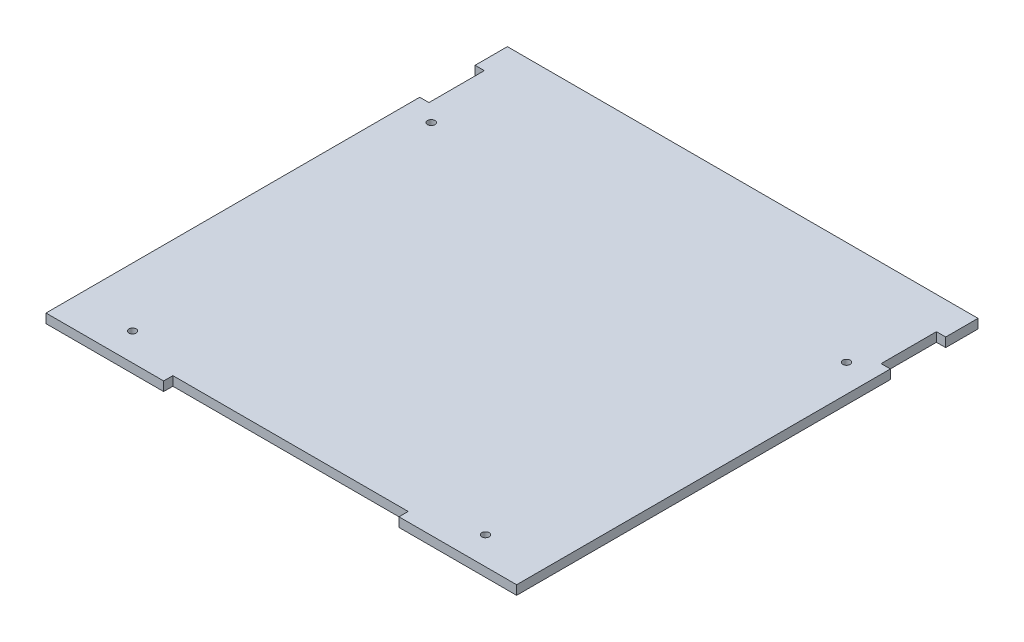
SolidWorks part; units mm, degrees
ref_plane "Front Plane" through (0, 0, 0) normal (0, 0, 1) x (1, 0, 0)
ref_plane "Top Plane" through (0, 0, 0) normal (0, 1, 0) x (1, 0, 0)
ref_plane "Right Plane" through (0, 0, 0) normal (1, 0, 0) x (0, 0, -1)
sketch "Sketch2" plane through (0, 0, 0) normal (0, 1, 0) x (1, 0, 0)
  line L1 (0, 0) -> (255, 0)
  line L2 (0, 0) -> (0, 65)
  line L3 (0, 65) -> (255, 65)
  line L4 (255, 0) -> (255, 65)
extrude "Boss-Extrude1" add sketch "Sketch2" along normal blind 5
sketch "Sketch3" plane through (0, 5, 0) normal (0, 1, 0) x (1, 0, 0)
  line L0 (255, 65) -> (261, 65)
  line L1 (261, 65) -> (261, 0)
  line L2 (261, 0) -> (255, 0)
  line L3 (255, 0) -> (255, 65)
  line L4 (255, 0) -> (255, 17.5)
  line L5 (255, 0) -> (255, 17.5)
  line L6 (255, 17.5) -> (250, 17.5)
  line L7 (250, 17.5) -> (250, 47.5)
  line L8 (250, 47.5) -> (255, 47.5)
  line L9 (255, 47.5) -> (255, 17.5)
  line L10 (127.5, 65) -> (127.5, 23.845)
  line L11 (255, 65) -> (0, 65) construction
  line L12 (0, 47.5) -> (0, 17.5)
  line L13 (5, 47.5) -> (0, 47.5)
  line L14 (5, 17.5) -> (5, 47.5)
  line L15 (0, 17.5) -> (5, 17.5)
  line L16 (0, 0) -> (0, 17.5)
  line L17 (0, 0) -> (0, 17.5)
  line L18 (0, 0) -> (0, 65)
  line L19 (-6, 0) -> (0, 0)
  line L20 (-6, 65) -> (-6, 0)
  line L21 (0, 65) -> (-6, 65)
  line M8 (255, 0) -> (255, 65)
extrude "Boss-Extrude2" add sketch "Sketch3" against normal up to surface (5 mm away) contours L2 L1 L0 L3 M8 | L18 L21 L20 L19 region at (258, 5, -32.5) up to face at (127.5, 0, -32.5)
extrude "Cut-Extrude1" cut sketch "Sketch3<3>" against normal blind 10 contours L15 L14 L13 L12 | L6 L7 L8 L9
sketch "Sketch3<3>" plane through (0, 5, 0) normal (0, 1, 0) x (1, 0, 0) same geometry as "Sketch3"
sketch "Sketch4" plane through (0, 0, 0) normal (0, -1, 0) x (1, 0, 0)
  line L0 (255, -47.5) -> (255, -65)
  line L1 (261, -65) -> (-6, -65) construction
  line L2 (255, -65) -> (261, -65)
  line L3 (261, -65) -> (261, 0)
  line L4 (261, 0) -> (255, 0)
  line L5 (-6, 0) -> (261, 0) construction
  line L6 (255, 0) -> (255, -47.5)
  line L8 (-6, -65) -> (0, -65)
  line L9 (-6, -65) -> (-6, 0)
  line L10 (-6, 0) -> (0, 0)
  line L11 (0, -65) -> (0, 0)
extrude "Cut-Extrude2" cut sketch "Sketch4" against normal blind 10
sketch "Sketch6" plane through (0, 0, 0) normal (0, 0, 1) x (1, 0, 0)
  line L1 (255, 0) -> (0, 0)
  line L2 (255, 0) -> (255, 5)
  line L3 (255, 5) -> (0, 5)
  line L4 (0, 0) -> (0, 5)
extrude "Boss-Extrude3" add sketch "Sketch6" along normal blind 185
sketch "Sketch8" plane through (0, 5, 0) normal (0, 1, 0) x (1, 0, 0)
  line L0 (255, -185) -> (0, -185) construction
  line L1 (127.5, -185) -> (191.25, -185)
  line L3 (127.5, -180) -> (191.25, -180)
  line L7 (127.5, -185) -> (63.75, -185)
  line L9 (127.5, -180) -> (63.75, -180)
  line L11 (191.25, -185) -> (191.25, -180)
  line L12 (63.75, -180) -> (63.75, -185)
extrude "Cut-Extrude3" cut sketch "Sketch8" against normal blind 185
sketch "Sketch9" plane through (0, 5, 0) normal (0, 1, 0) x (1, 0, 0)
  line L0 (223.125, -185) -> (223.125, -170)
  line L1 (255, -185) -> (191.25, -185) construction
  line L2 (127.5, -180) -> (127.5, -159.0905)
  line L3 (191.25, -180) -> (63.75, -180) construction
  circle A0 centre (223.125, -170) radius 1.5
  circle A1 centre (31.875, -170) radius 1.5
extrude "Cut-Extrude4" cut sketch "Sketch9" against normal blind 185 contours A0 | A1 region at (224.1557, 5, 171.0307) region at (31.875, 5, 170)
sketch "Sketch10" plane through (0, 5, 0) normal (0, 1, 0) x (1, 0, 0)
  line L0 (255, 17.5) -> (255, 0)
  line L1 (255, -185) -> (255, 17.5) construction
  line L2 (255, 8.75) -> (240, 8.75)
  line L3 (127.5, 65) -> (127.5, -19.5233)
  line L4 (255, 65) -> (0, 65) construction
  circle A0 centre (240, 8.75) radius 1.5
  circle A1 centre (15, 8.75) radius 1.5
extrude "Cut-Extrude5" cut sketch "Sketch10" against normal blind 185 contours A0 | A1 region at (238.5424, 5, -8.75) region at (15, 5, -8.75)
sketch "Sketch11" plane through (0, 5, 0) normal (0, 1, 0) x (1, 0, 0)
  circle A0 centre (240, 8.75) radius 2
  circle A1 centre (15, 8.75) radius 2
  circle A2 centre (31.875, -170) radius 2
  circle A3 centre (223.125, -170) radius 2
extrude "Cut-Extrude6" cut sketch "Sketch11" against normal blind 10
